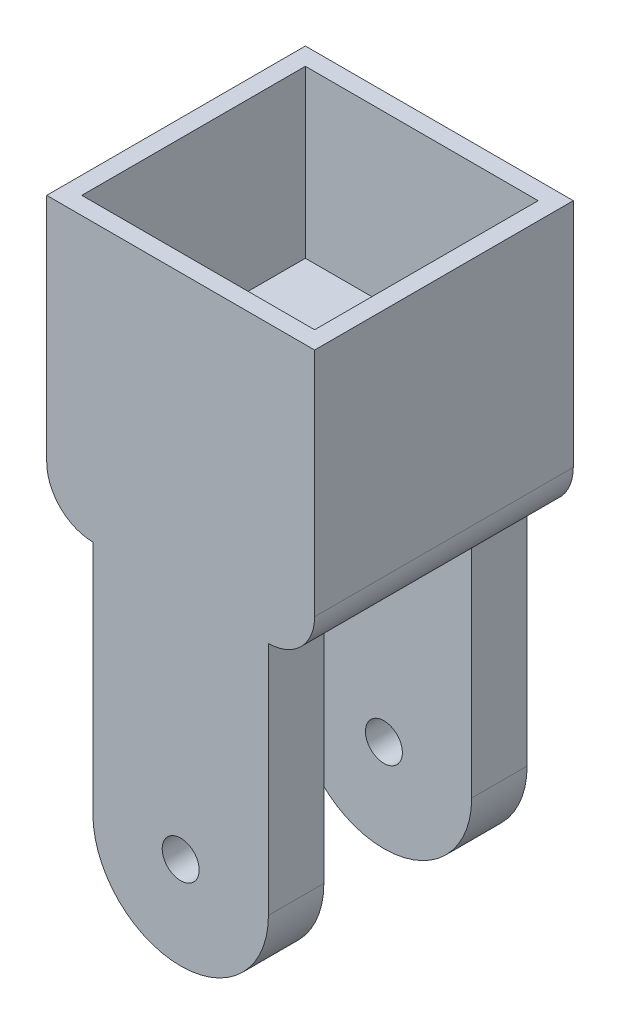
SolidWorks part; units mm, degrees
ref_plane "前视基准面" through (0, 0, 0) normal (0, 0, 1) x (1, 0, 0)
ref_plane "上视基准面" through (0, 0, 0) normal (0, 1, 0) x (1, 0, 0)
ref_plane "右视基准面" through (0, 0, 0) normal (1, 0, 0) x (0, 0, -1)
other "Configuration Table"
sketch "草图1" plane through (0, 0, 0) normal (0, 1, 0) x (1, 0, 0)
  line L1 (-14.5, -14) -> (14.5, -14)
  line L2 (-14.5, -14) -> (-14.5, 14)
  line L3 (-14.5, 14) -> (14.5, 14)
  line L4 (14.5, -14) -> (14.5, 14)
  line L5 (-14.5, -14) -> (14.5, 14) construction
  line L6 (-14.5, 14) -> (14.5, -14) construction
  point P0 (0, 0)
  point P9 (0, 0)
  dimension "D1" = 28
  dimension "D2" = 29
extrude "凸台-拉伸3" add sketch "草图1" along normal blind 30 contours L2 L1 L4 L3
sketch "草图2" plane through (0, 0, 0) normal (0, -1, 0) x (1, 0, 0)
  line L0 (-14.5, -14) -> (14.5, -14) construction
  line L1 (-9.5, -14) -> (9.5, -14)
  line L2 (-9.5, -14) -> (-9.5, -8)
  line L3 (-9.5, -8) -> (9.5, -8)
  line L4 (9.5, -14) -> (9.5, -8)
  line L6 (-14.5, 14) -> (14.5, 14) construction
  line L7 (-9.5, 14) -> (9.5, 14)
  line L8 (-9.5, 14) -> (-9.5, 8)
  line L9 (-9.5, 8) -> (9.5, 8)
  line L10 (9.5, 14) -> (9.5, 8)
  line L11 (-14.5, 14) -> (-14.5, -14) construction
  line L12 (14.5, 14) -> (14.5, -14) construction
  dimension "D1" = 6
  dimension "D2" = 5
  dimension "D3" = 5
extrude "凸台-拉伸4" add sketch "草图2" along normal blind 35
sketch "草图3" plane through (0, 0, -14) normal (0, 0, -1) x (-1, 0, 0)
  line L0 (9.5, -35) -> (-9.5, -35) construction
  circle A0 centre (0, -25) radius 2
  dimension "D2" = 4
  dimension "D1" = 10
extrude "切除-拉伸3" cut sketch "草图3" against normal through all
sketch "草图4" plane through (0, 30, 0) normal (0, 1, 0) x (1, 0, 0)
  line L0 (-14.5, -14) -> (14.5, -14) construction
  line L1 (12.6, -12.1) -> (-12.6, -12.1)
  line L2 (12.6, -12.1) -> (12.6, 12.1)
  line L3 (12.6, 12.1) -> (-12.6, 12.1)
  line L4 (-12.6, -12.1) -> (-12.6, 12.1)
  line L5 (12.6, -12.1) -> (-12.6, 12.1) construction
  line L6 (12.6, 12.1) -> (-12.6, -12.1) construction
  line L7 (14.5, -14) -> (14.5, 14) construction
  circle A0 centre (0, 0) radius 5.1
  point P7 (0, 0)
  dimension "D3" = 10.2
  dimension "D1" = 1.9
  dimension "D2" = 1.9
extrude "切除-拉伸4" cut sketch "草图4" against normal offset from surface (18 mm away) 12 contours L4 L3 L2 L1 up to face at (0, 0, 0)
extrude "切除-拉伸5" cut sketch "草图4<3>" against normal blind 10 from surface contours A0 starting at face at (0, 12, 0)
sketch "草图4<3>" plane through (0, 30, 0) normal (0, 1, 0) x (1, 0, 0) same geometry as "草图4"
fillet "圆角1" radius 5 2 edges at (-14.5, 0, 0) (14.5, 0, 0)
fillet "圆角2" radius 9.5 4 edges at (9.5, -35, -11) (-9.5, -35, -11) (9.5, -35, 11) (-9.5, -35, 11)
